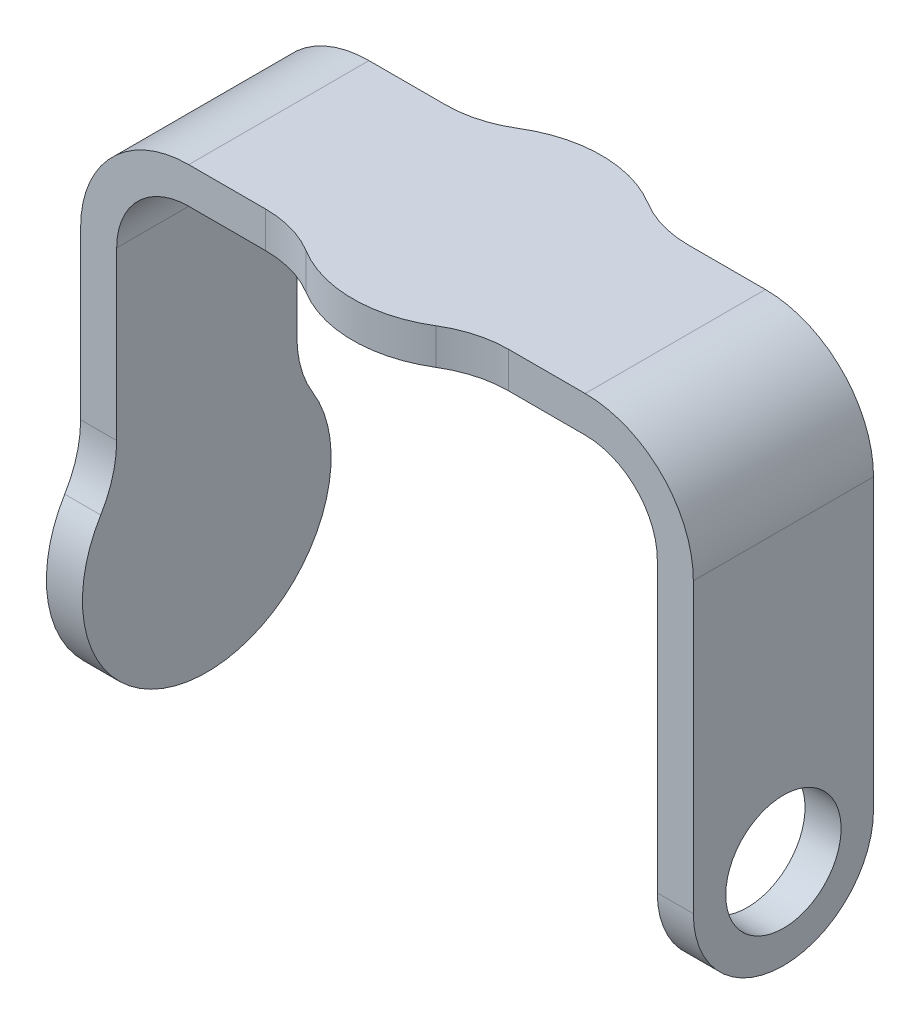
SolidWorks part; units mm, degrees
ref_plane "Front Plane" through (0, 0, 0) normal (0, 0, 1) x (1, 0, 0)
ref_plane "Top Plane" through (0, 0, 0) normal (0, 1, 0) x (1, 0, 0)
ref_plane "Right Plane" through (0, 0, 0) normal (1, 0, 0) x (0, 0, -1)
sketch "Sketch2" plane through (0, 0, 0) normal (0, 0, 1) x (1, 0, 0)
  line L0 (-37.5, -67.25) -> (-37.5, -10)
  line L1 (-27.5, 0) -> (27.5, 0)
  line L2 (37.5, -10) -> (37.5, -67.25)
  line L3 (37.5, -67.25) -> (42.5, -67.25)
  line L4 (42.5, -67.25) -> (42.5, -10)
  line L5 (27.5, 5) -> (-27.5, 5)
  line L6 (-42.5, -10) -> (-42.5, -67.25)
  line L7 (-42.5, -67.25) -> (-37.5, -67.25)
  arc A0 (27.5, 0) -> (37.5, -10) centre (27.5, -10) cw
  arc A1 (-37.5, -10) -> (-27.5, 0) centre (-27.5, -10) cw
  arc A2 (-27.5, 5) -> (-42.5, -10) centre (-27.5, -10) ccw
  arc A3 (42.5, -10) -> (27.5, 5) centre (27.5, -10) ccw
  point P2 (0, 0)
  point P12 (37.5, 0)
  point P15 (-37.5, 0)
  dimension "D5" = 10
  dimension "D6" = 15
  dimension "D1" = 75
  dimension "D2" = 5
  dimension "D3" = 5
  dimension "D4" = 67.25
extrude "Bracket U-shape" add sketch "Sketch2" along normal mid plane 25
sketch "Sketch3" plane through (0, 5, 0) normal (0, 1, 0) x (1, 0, 0)
  circle A0 centre (0, 0) radius 17.25
  dimension "D1" = 34.5
extrude "Motor ring" add sketch "Sketch3" against normal blind 5
fillet "Motor ring fillets 15mm" radius 15 4 edges at (11.8875, 2.5, 12.5) (-11.8875, 2.5, 12.5) (-11.8875, 2.5, -12.5) (11.8875, 2.5, -12.5)
fillet "U bracket bottom rounding 12.5mm" radius 12.5 4 edges at (40, -67.25, 12.5) (40, -67.25, -12.5) (-40, -67.25, -12.5) (-40, -67.25, 12.5)
sketch "Sketch4" plane through (-42.5, 0, 0) normal (-1, 0, 0) x (0, 0, 1)
  circle A0 centre (0, -50) radius 17.25
  point P2 (0, 0)
  dimension "D1" = 34.5
  dimension "D2" = 50
extrude "Tilt motor tab" add sketch "Sketch4" against normal blind 5
fillet "Tilt motor tab fillets 15mm" radius 15 2 edges at (-40, -38.1125, -12.5) (-40, -38.1125, 12.5)
sketch "Sketch6" plane through (37.5, 0, 0) normal (-1, 0, 0) x (0, 0, 1)
  line L0 (-12.5, -54.75) -> (-12.5, -10) construction
  line L1 (12.5, -54.75) -> (12.5, -50)
  line L2 (-12.5, -54.75) -> (-12.5, -50)
  circle A0 centre (0, -50) radius 8
  arc A2 (-14.7093, -40.989) -> (14.7093, -40.989) centre (0, -50) ccw construction
  arc A3 (-12.5, -50) -> (12.5, -50) centre (0, -50) ccw
  arc A4 (-12.5, -54.75) -> (0, -67.25) centre (0, -54.75) ccw construction
  arc A5 (0, -67.25) -> (12.5, -54.75) centre (0, -54.75) ccw construction
  arc A6 (-12.5, -54.75) -> (0, -67.25) centre (0, -54.75) ccw
  arc A7 (0, -67.25) -> (12.5, -54.75) centre (0, -54.75) ccw
  dimension "D1" = 16
extrude "Bearing hole cut" cut sketch "Sketch6" against normal through all body kept at (-37.5, -33.1533, -12.5)
